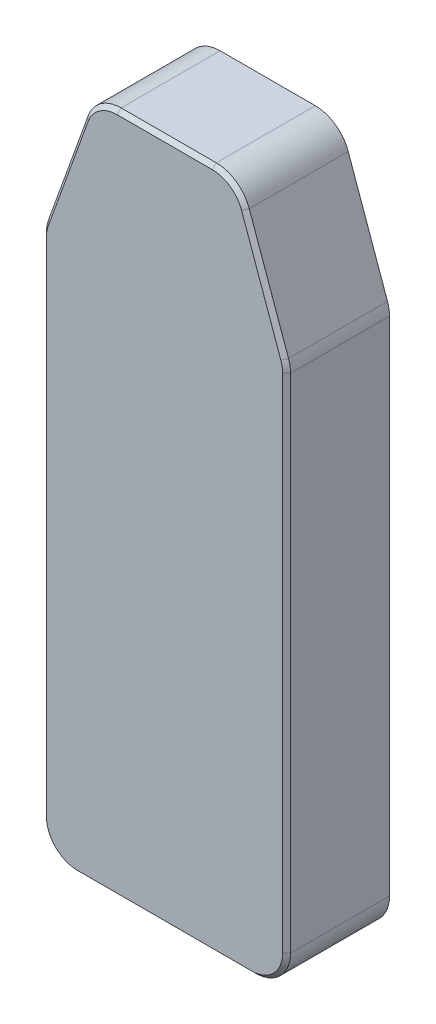
SolidWorks part; units mm, degrees
ref_plane "Front Plane" through (0, 0, 0) normal (0, 0, 1) x (1, 0, 0)
ref_plane "Top Plane" through (0, 0, 0) normal (0, 1, 0) x (1, 0, 0)
ref_plane "Right Plane" through (0, 0, 0) normal (1, 0, 0) x (0, 0, -1)
sketch "Sketch1" plane through (0, 0, 0) normal (0, 0, 1) x (1, 0, 0)
  line L6 (-42.6423, 80.729) -> (-27.5892, 122.4768)
  line L7 (-43.25, -113) -> (-43.25, 77.2522)
  line L8 (-42.6423, 80.729) -> (-27.5892, 122.4768)
  line L9 (-43.25, -113) -> (-43.25, 77.2522)
  line L11 (-43.25, -113) -> (-43.25, 77.2522)
  line L12 (-43.25, -113) -> (-43.25, 77.2522)
  line L36 (43.25, -113) -> (43.25, 77.2693)
  line L37 (42.6538, 80.7141) -> (27.763, 122.4448)
  line L38 (18.1092, 129.25) -> (-17.9469, 129.25)
  line L39 (-27.5892, 122.4768) -> (-42.6423, 80.729)
  line L40 (-43.25, 77.2522) -> (-43.25, -113)
  line L41 (-33, -123.25) -> (33, -123.25)
  line L43 (46.25, -113) -> (46.25, 77.2693)
  line L44 (45.4793, 81.7223) -> (30.5885, 123.453)
  line L45 (18.1092, 132.25) -> (-17.9469, 132.25)
  line L46 (-30.4113, 123.4944) -> (-45.4645, 81.7466)
  line L47 (-46.25, 77.2522) -> (-46.25, -113)
  line L48 (-33, -126.25) -> (33, -126.25)
  arc A3 (-42.6423, 80.729) -> (-43.25, 77.2522) centre (-33, 77.2522) ccw
  arc A4 (-42.6423, 80.729) -> (-43.25, 77.2522) centre (-33, 77.2522) ccw
  arc A6 (-42.6423, 80.729) -> (-43.25, 77.2522) centre (-33, 77.2522) ccw
  arc A7 (-42.6423, 80.729) -> (-43.25, 77.2522) centre (-33, 77.2522) ccw
  arc A31 (33, -123.25) -> (43.25, -113) centre (33, -113) ccw
  arc A32 (43.25, 77.2693) -> (42.6538, 80.7141) centre (33, 77.2693) ccw
  arc A33 (27.763, 122.4448) -> (18.1092, 129.25) centre (18.1092, 119) ccw
  arc A34 (-17.9469, 129.25) -> (-27.5892, 122.4768) centre (-17.9469, 119) ccw
  arc A35 (-42.6423, 80.729) -> (-43.25, 77.2522) centre (-33, 77.2522) ccw
  arc A36 (-43.25, -113) -> (-33, -123.25) centre (-33, -113) ccw
  arc A37 (33, -126.25) -> (46.25, -113) centre (33, -113) ccw
  arc A38 (46.25, 77.2693) -> (45.4793, 81.7223) centre (33, 77.2693) ccw
  arc A39 (30.5885, 123.453) -> (18.1092, 132.25) centre (18.1092, 119) ccw
  arc A40 (-17.9469, 132.25) -> (-30.4113, 123.4944) centre (-17.9469, 119) ccw
  arc A41 (-45.4645, 81.7466) -> (-46.25, 77.2522) centre (-33, 77.2522) ccw
  arc A42 (-46.25, -113) -> (-33, -126.25) centre (-33, -113) ccw
  dimension "D1" = 0.25
  dimension "D2" = 0.25
  dimension "D3" = 3
extrude "Boss-Extrude1" add sketch "Sketch1" along normal blind 36 contours L47 A42 L48 A37 L43 A38 L44 A39 L45 A40 L46 A41 A36 L9 A4 L8 A34 L38 A33 L37 A32 L36 A31 L41 region at (40.4278, -120.4278, 0)
sketch "Sketch3" plane through (0, 0, 36) normal (0, 0, 1) x (1, 0, 0)
  line L6 (-46.25, 77.2522) -> (-46.25, -113)
  line L7 (-33, -126.25) -> (33, -126.25)
  line L8 (46.25, -113) -> (46.25, 77.2693)
  line L9 (45.4793, 81.7223) -> (30.5885, 123.453)
  line L10 (18.1092, 132.25) -> (-17.9469, 132.25)
  line L11 (-30.4113, 123.4944) -> (-45.4645, 81.7466)
  line L12 (-46.25, 77.2522) -> (-46.25, -113)
  line L13 (-33, -126.25) -> (33, -126.25)
  line L14 (46.25, -113) -> (46.25, 77.2693)
  line L15 (45.4793, 81.7223) -> (30.5885, 123.453)
  line L16 (18.1092, 132.25) -> (-17.9469, 132.25)
  line L17 (-30.4113, 123.4944) -> (-45.4645, 81.7466)
  arc A6 (-46.25, -113) -> (-33, -126.25) centre (-33, -113) ccw
  arc A7 (33, -126.25) -> (46.25, -113) centre (33, -113) ccw
  arc A8 (46.25, 77.2693) -> (45.4793, 81.7223) centre (33, 77.2693) ccw
  arc A9 (30.5885, 123.453) -> (18.1092, 132.25) centre (18.1092, 119) ccw
  arc A10 (-17.9469, 132.25) -> (-30.4113, 123.4944) centre (-17.9469, 119) ccw
  arc A11 (-45.4645, 81.7466) -> (-46.25, 77.2522) centre (-33, 77.2522) ccw
  arc A12 (-46.25, -113) -> (-33, -126.25) centre (-33, -113) ccw
  arc A13 (33, -126.25) -> (46.25, -113) centre (33, -113) ccw
  arc A14 (46.25, 77.2693) -> (45.4793, 81.7223) centre (33, 77.2693) ccw
  arc A15 (30.5885, 123.453) -> (18.1092, 132.25) centre (18.1092, 119) ccw
  arc A16 (-17.9469, 132.25) -> (-30.4113, 123.4944) centre (-17.9469, 119) ccw
  arc A17 (-45.4645, 81.7466) -> (-46.25, 77.2522) centre (-33, 77.2522) ccw
  dimension "D1" = 0
extrude "Boss-Extrude2" add sketch "Sketch3" along normal blind 3
chamfer "Chamfer1" distance 1.5 angle 45 24 edges at (-37.9379, 102.6205, 39) (-25.563, 129.8423, 39) (0.0812, 132.25, 39) (25.7433, 129.8297, 39) (38.0339, 102.5876, 39) (46.0559, 79.5289, 39) (46.25, -17.8654, 39) (42.3692, -122.3692, 39) (0, -126.25, 39) (-42.3692, -122.3692, 39) (-46.25, -17.8739, 39) (-46.0521, 79.5335, 39) (35.2084, 101.5794, 0) (43.0999, 79.0173, 0) (24.0148, 127.3777, 0) (43.25, -17.8654, 0) (0.0812, 129.25, 0) (40.2478, -120.2478, 0) (-23.8386, 127.3875, 0) (0, -123.25, 0) (-35.1158, 101.6029, 0) (-40.2478, -120.2478, 0) (-43.0969, 79.0169, 0) (-43.25, -17.8739, 0)
